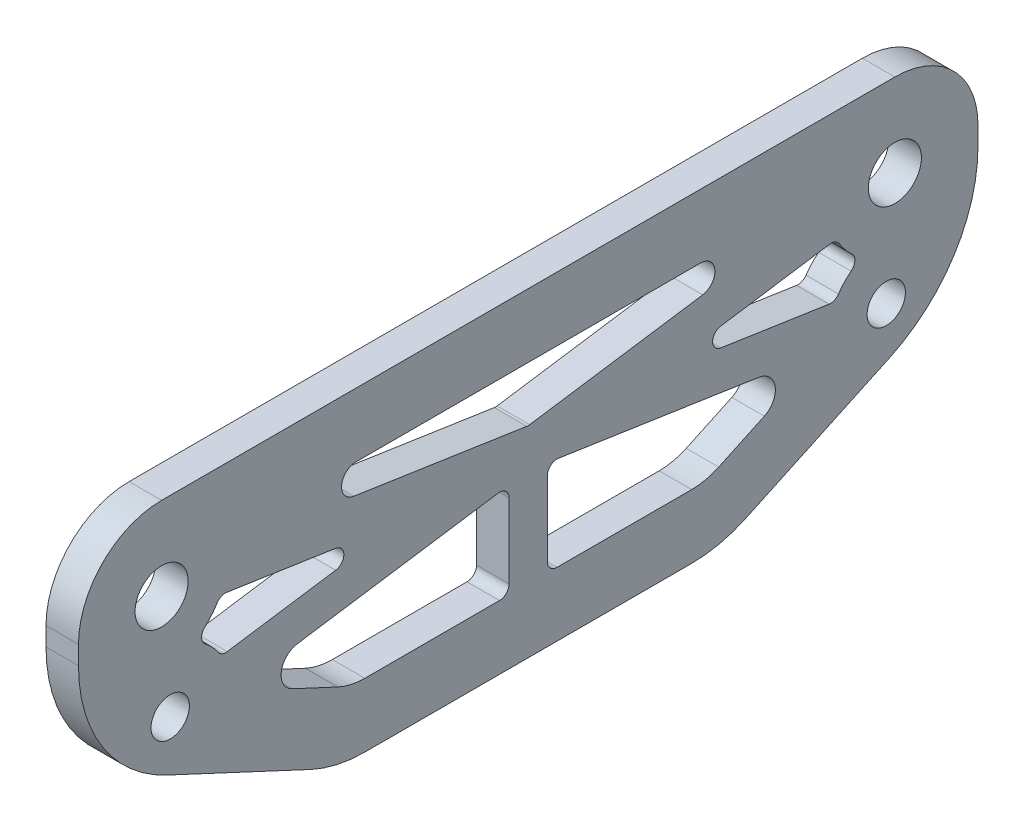
SolidWorks part; units mm, degrees
ref_plane "Front Plane" through (0, 0, 0) normal (0, 0, 1) x (1, 0, 0)
ref_plane "Top Plane" through (0, 0, 0) normal (0, 1, 0) x (1, 0, 0)
ref_plane "Right Plane" through (0, 0, 0) normal (1, 0, 0) x (0, 0, -1)
sketch "Sketch1" plane through (0, 0, 0) normal (1, 0, 0) x (0, 0, -1)
  line L0 (15, 12.5) -> (28.675, 12.5)
  line L1 (-15, -12.5) -> (15, -12.5)
  line L3 (-15, 12.5) -> (15, 12.5)
  line L5 (-15, -12.5) -> (15, 12.5) construction
  line L6 (-15, 12.5) -> (15, -12.5) construction
  line L8 (0, 12.5) -> (0, -12.5) construction
  line L10 (-15, 12.5) -> (-28.675, 12.5)
  line L11 (23.175, 193.0853) -> (23.175, -34.3147) construction
  line L13 (35.175, 6) -> (35.175, 4.5526)
  line L14 (28.2464, -6.3231) -> (15, -12.5)
  line L16 (-35.175, 6) -> (-35.175, 4.5526)
  line L17 (-28.2464, -6.3231) -> (-15, -12.5)
  arc A0 (28.675, 12.5) -> (35.175, 6) centre (28.675, 6) cw
  circle A1 centre (28.675, 6) radius 5.5 construction
  circle A2 centre (-28.675, 6) radius 5.5 construction
  arc A3 (-28.675, 12.5) -> (-35.175, 6) centre (-28.675, 6) ccw
  arc A4 (35.175, 4.5526) -> (28.2464, -6.3231) centre (23.175, 4.5526) cw
  circle A5 centre (28.675, 6) radius 2.075
  arc A6 (-35.175, 4.5526) -> (-28.2464, -6.3231) centre (-23.175, 4.5526) ccw
  circle A9 centre (-28.675, 6) radius 2.075
  circle A11 centre (28, -2.5) radius 1.5
  circle A12 centre (-28, -2.5) radius 1.5
  point P0 (0, 0)
  point P28 (0, 0)
  dimension "D1" = 11
  dimension "D2" = 1
  dimension "D3" = 4.15
  dimension "D4" = 3
  dimension "D6" = 25
  dimension "D8" = 12
  dimension "D5" = 25
  dimension "D7" = 30
  dimension "D9" = 28
  dimension "D10" = 2.5
extrude "Boss-Extrude1" add sketch "Sketch1" along normal blind 2.54
fillet "Fillet1" radius 10 2 edges at (1.27, -12.5, -15) (1.27, -12.5, 15)
sketch "Sketch2" plane through (0, 0, 0) normal (1, 0, 0) x (0, 0, -1)
  line L0 (-28.675, 6) -> (28, -2.5) construction
  line L10 (-28.675, -2.6012) -> (28.675, 6)
  line L11 (-28.675, 6) -> (28, -2.5)
  line L12 (-28.8975, 4.5166) -> (27.7775, -3.9834)
  line L13 (-28.4525, 7.4834) -> (28.2225, -1.0166)
  line L14 (-28.8975, 4.5166) -> (-28.4525, 7.4834)
  line L15 (27.7775, -3.9834) -> (28.2225, -1.0166)
  line L16 (-12.7831, -7.5) -> (12.7831, -7.5)
  line L17 (14.8961, -7.0315) -> (26.1333, -1.7916)
  line L18 (30.175, 4.5526) -> (30.175, 6)
  line L19 (28.675, 7.5) -> (-28.675, 7.5)
  line L20 (-30.175, 6) -> (-30.175, 4.5526)
  line L21 (-26.1333, -1.7916) -> (-14.8961, -7.0315)
  line L22 (-12.7831, -7.5) -> (12.7831, -7.5)
  line L23 (14.8961, -7.0315) -> (26.1333, -1.7916)
  line L24 (30.175, 4.5526) -> (30.175, 6)
  line L25 (28.675, 7.5) -> (-28.675, 7.5)
  line L26 (-30.175, 6) -> (-30.175, 4.5526)
  line L27 (-26.1333, -1.7916) -> (-14.8961, -7.0315)
  line L28 (-28.4525, -4.0846) -> (28.8975, 4.5166)
  line L29 (-28.8975, -1.1178) -> (28.4525, 7.4834)
  line L30 (-28.4525, -4.0846) -> (-28.8975, -1.1178)
  line L31 (28.8975, 4.5166) -> (28.4525, 7.4834)
  line L32 (0, -7.5) -> (0, 7.5) construction
  line L33 (0, 1.6994) -> (0, -7.5)
  line L34 (-1.5, 1.6994) -> (-1.5, -7.5)
  line L35 (1.5, 1.6994) -> (1.5, -7.5)
  line L36 (-1.5, 1.6994) -> (1.5, 1.6994)
  line L37 (-1.5, -7.5) -> (1.5, -7.5)
  arc A0 (-18.0527, -2.5249) -> (-18.4641, -5.3678) centre (-17.8302, -4.0083) ccw
  arc A1 (18.0527, -2.5249) -> (18.4641, -5.3678) centre (17.8302, -4.0083) cw
  circle A2 centre (-28, -2.5) radius 4.5
  circle A3 centre (-28, -2.5) radius 4.5
  circle A5 centre (28, -2.5) radius 4.5
  circle A6 centre (28, -2.5) radius 4.5
  circle A11 centre (-28.675, 6) radius 5.075
  arc A12 (12.7831, -7.5) -> (14.8961, -7.0315) centre (12.7831, -2.5) ccw
  arc A13 (26.1333, -1.7916) -> (30.175, 4.5526) centre (23.175, 4.5526) ccw
  arc A14 (30.175, 6) -> (28.675, 7.5) centre (28.675, 6) ccw
  arc A15 (-28.675, 7.5) -> (-30.175, 6) centre (-28.675, 6) ccw
  arc A16 (-30.175, 4.5526) -> (-26.1333, -1.7916) centre (-23.175, 4.5526) ccw
  arc A17 (-14.8961, -7.0315) -> (-12.7831, -7.5) centre (-12.7831, -2.5) ccw
  arc A18 (12.7831, -7.5) -> (14.8961, -7.0315) centre (12.7831, -2.5) ccw
  arc A19 (26.1333, -1.7916) -> (30.175, 4.5526) centre (23.175, 4.5526) ccw
  arc A20 (30.175, 6) -> (28.675, 7.5) centre (28.675, 6) ccw
  arc A21 (-28.675, 7.5) -> (-30.175, 6) centre (-28.675, 6) ccw
  arc A22 (-30.175, 4.5526) -> (-26.1333, -1.7916) centre (-23.175, 4.5526) ccw
  arc A23 (-14.8961, -7.0315) -> (-12.7831, -7.5) centre (-12.7831, -2.5) ccw
  circle A24 centre (-28.675, 6) radius 5.075
  circle A26 centre (28.675, 6) radius 5.075
  circle A27 centre (28.675, 6) radius 5.075
  arc A32 (13.477, 7.5) -> (13.6439, 5.2624) centre (13.477, 6.375) cw
  arc A33 (-13.477, 7.5) -> (-13.6439, 5.2624) centre (-13.477, 6.375) ccw
  dimension "D11" = 3
  dimension "D12" = 1.125
  dimension "D2" = 1.5
  dimension "D1" = 5
  dimension "D3" = 3
  dimension "D4" = 3
  dimension "D6" = 1.5
  dimension "D7" = 1.5
  dimension "D8" = 1.5
  dimension "D9" = 1.5
  dimension "D13" = 1.5
  dimension "D14" = 1.5
  dimension "D15" = 3
extrude "Cut-Extrude2" cut sketch "Sketch2" along normal through all contours A24 A3 L29 L12 | A27 L28 L13 A6 | L25 A33 L13 L29 A32 | A1 L12 L35 L22 | L28 A0 L22 L34 region at (0, 1.7005, 19.9688) region at (0, -4.2389, 9.1911) region at (0, 5.8357, 0) region at (0, -4.2389, -9.1911) region at (0, 1.7005, -19.9688)
fillet "Fillet2" radius 0.75 13 edges at (1.27, -7.5, -1.5) (1.27, 3.7975, -24.1028) (1.27, 1.6994, -10.1133) (1.27, 3.7975, 24.1028) (1.27, 3.2162, 0) (1.27, -0.0424, -1.5) (1.27, -7.5, 1.5) (1.27, -0.0424, 1.5) (1.27, 1.6994, 10.1133) (1.27, -0.3873, -24.0268) (1.27, 1.6002, -26.1457) (1.27, -0.3873, 24.0268) (1.27, 1.6002, 26.1457)
